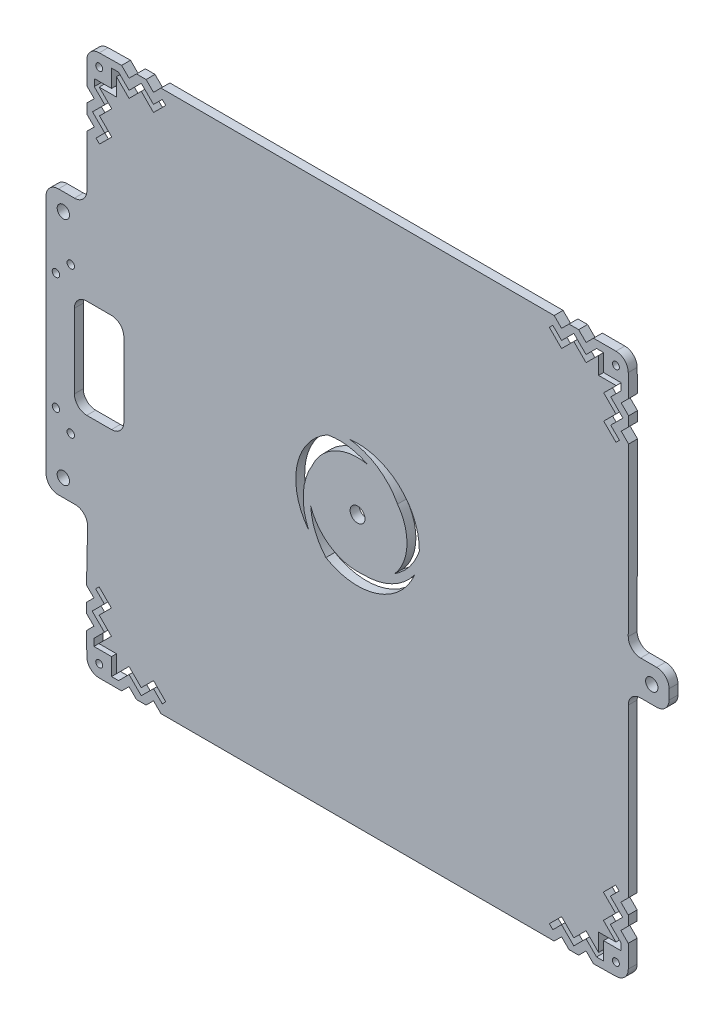
SolidWorks part; units mm, degrees
ref_plane "Front Plane" through (0, 0, 0) normal (0, 0, 1) x (1, 0, 0)
ref_plane "Top Plane" through (0, 0, 0) normal (0, 1, 0) x (1, 0, 0)
ref_plane "Right Plane" through (0, 0, 0) normal (1, 0, 0) x (0, 0, -1)
sketch "Model" plane through (0, 0, 0) normal (0, 0, 1) x (1, 0, 0)
  line L0 (-4, 125.6) -> (2.5, 125.6)
  line L1 (-4, 18.4) -> (2.8123, 18.4)
  line L2 (-9, 120.6) -> (-9, 23.4)
  line L3 (231.5, 82) -> (231.6, 82)
  line L4 (243, 74) -> (243, 70)
  line L5 (231.5, 62) -> (231.6, 62)
  line L10 (7.5, 151.5294) -> (7.5, 130.6)
  line L11 (7.5, 161.4289) -> (7.5, 157.5294)
  line L12 (7.5, 176.5) -> (7.5, 167.4289)
  line L13 (27.5711, 181.6421) -> (31.4706, 181.6421)
  line L14 (27.5711, -37.5) -> (31.4706, -37.5)
  line L15 (12.5, -37.5) -> (21.5711, -37.5)
  line L16 (7.3579, -17.4289) -> (7.3579, -13.5294)
  line L17 (226.5, -17.4289) -> (226.5, -13.5294)
  line L18 (226.5, -32.5) -> (226.5, -23.4289)
  line L19 (206.4289, -37.6421) -> (202.5294, -37.6421)
  line L20 (206.4289, 181.5) -> (202.5294, 181.5)
  line L21 (221.5, 181.5) -> (212.4289, 181.5)
  line L22 (226.6421, 161.4289) -> (226.6421, 157.5294)
  line L23 (14.7426, 154.5294) -> (9.7929, 159.4792)
  line L24 (14.7426, 164.4289) -> (9.7929, 159.4792)
  line L25 (17.5711, 164.4289) -> (12.6213, 159.4792)
  line L26 (17.5711, 154.5294) -> (12.6213, 159.4792)
  line L27 (17.5711, 164.4289) -> (12.5, 169.5)
  line L28 (14.7426, 164.4289) -> (10.5, 168.6716)
  line L29 (10.5, 168.6716) -> (10.5, 171.5)
  line L30 (10.5, 164.4289) -> (7.5, 161.4289)
  line L31 (10.5, 164.4289) -> (7.5, 167.4289)
  line L32 (10.5, 154.5294) -> (7.5, 151.5294)
  line L33 (10.5, 154.5294) -> (7.5, 157.5294)
  line L34 (34.4706, 174.3995) -> (29.5208, 179.3492)
  line L35 (24.5711, 174.3995) -> (29.5208, 179.3492)
  line L36 (24.5711, 171.5711) -> (29.5208, 176.5208)
  line L37 (34.4706, 171.5711) -> (29.5208, 176.5208)
  line L38 (24.5711, 171.5711) -> (19.5, 176.6421)
  line L39 (24.5711, 174.3995) -> (20.3284, 178.6421)
  line L40 (20.3284, 178.6421) -> (17.5, 178.6421)
  line L41 (24.5711, 178.6421) -> (27.5711, 181.6421)
  line L42 (24.5711, 178.6421) -> (21.5711, 181.6421)
  line L43 (34.4706, 178.6421) -> (37.4706, 181.6421)
  line L44 (34.4706, 178.6421) -> (31.4706, 181.6421)
  line L45 (17.5, 178.6421) -> (17.5, 171.5)
  line L46 (10.5, 171.5) -> (17.5, 171.5)
  line L47 (19.5, 176.6421) -> (19.5, 169.5)
  line L48 (12.5, 169.5) -> (19.5, 169.5)
  line L49 (21.5711, 181.6421) -> (12.5, 181.5)
  line L50 (34.4706, -30.2574) -> (29.5208, -35.2071)
  line L51 (24.5711, -30.2574) -> (29.5208, -35.2071)
  line L52 (24.5711, -27.4289) -> (29.5208, -32.3787)
  line L53 (34.4706, -27.4289) -> (29.5208, -32.3787)
  line L54 (24.5711, -27.4289) -> (19.5, -32.5)
  line L55 (24.5711, -30.2574) -> (20.3284, -34.5)
  line L56 (20.3284, -34.5) -> (17.5, -34.5)
  line L57 (24.5711, -34.5) -> (27.5711, -37.5)
  line L58 (24.5711, -34.5) -> (21.5711, -37.5)
  line L59 (34.4706, -34.5) -> (37.4706, -37.5)
  line L60 (34.4706, -34.5) -> (31.4706, -37.5)
  line L61 (14.6005, -10.5294) -> (9.6508, -15.4792)
  line L62 (14.6005, -20.4289) -> (9.6508, -15.4792)
  line L63 (17.4289, -20.4289) -> (12.4792, -15.4792)
  line L64 (17.4289, -10.5294) -> (12.4792, -15.4792)
  line L65 (17.4289, -20.4289) -> (12.3579, -25.5)
  line L66 (14.6005, -20.4289) -> (10.3579, -24.6716)
  line L67 (10.3579, -24.6716) -> (10.3579, -27.5)
  line L68 (10.3579, -20.4289) -> (7.3579, -17.4289)
  line L69 (10.3579, -20.4289) -> (7.3579, -23.4289)
  line L70 (10.3579, -10.5294) -> (7.3579, -7.5294)
  line L71 (10.3579, -10.5294) -> (7.3579, -13.5294)
  line L72 (10.3579, -27.5) -> (17.5, -27.5)
  line L73 (17.5, -34.5) -> (17.5, -27.5)
  line L74 (12.3579, -25.5) -> (19.5, -25.5)
  line L75 (19.5, -32.5) -> (19.5, -25.5)
  line L76 (7.3579, -23.4289) -> (7.5, -32.5)
  line L77 (219.2574, -10.5294) -> (224.2071, -15.4792)
  line L78 (219.2574, -20.4289) -> (224.2071, -15.4792)
  line L79 (216.4289, -20.4289) -> (221.3787, -15.4792)
  line L80 (216.4289, -10.5294) -> (221.3787, -15.4792)
  line L81 (216.4289, -20.4289) -> (221.5, -25.5)
  line L82 (219.2574, -20.4289) -> (223.5, -24.6716)
  line L83 (223.5, -24.6716) -> (223.5, -27.5)
  line L84 (223.5, -20.4289) -> (226.5, -17.4289)
  line L85 (223.5, -20.4289) -> (226.5, -23.4289)
  line L86 (223.5, -10.5294) -> (226.5, -7.5294)
  line L87 (223.5, -10.5294) -> (226.5, -13.5294)
  line L88 (199.5294, -30.3995) -> (204.4792, -35.3492)
  line L89 (209.4289, -30.3995) -> (204.4792, -35.3492)
  line L90 (209.4289, -27.5711) -> (204.4792, -32.5208)
  line L91 (199.5294, -27.5711) -> (204.4792, -32.5208)
  line L92 (209.4289, -27.5711) -> (214.5, -32.6421)
  line L93 (209.4289, -30.3995) -> (213.6716, -34.6421)
  line L94 (213.6716, -34.6421) -> (216.5, -34.6421)
  line L95 (209.4289, -34.6421) -> (206.4289, -37.6421)
  line L96 (209.4289, -34.6421) -> (212.4289, -37.6421)
  line L97 (199.5294, -34.6421) -> (196.5294, -37.6421)
  line L98 (199.5294, -34.6421) -> (202.5294, -37.6421)
  line L99 (216.5, -34.6421) -> (216.5, -27.5)
  line L100 (223.5, -27.5) -> (216.5, -27.5)
  line L101 (214.5, -32.6421) -> (214.5, -25.5)
  line L102 (221.5, -25.5) -> (214.5, -25.5)
  line L103 (212.4289, -37.6421) -> (221.5, -37.5)
  line L104 (199.5294, 174.2574) -> (204.4792, 179.2071)
  line L105 (209.4289, 174.2574) -> (204.4792, 179.2071)
  line L106 (209.4289, 171.4289) -> (204.4792, 176.3787)
  line L107 (199.5294, 171.4289) -> (204.4792, 176.3787)
  line L108 (209.4289, 171.4289) -> (214.5, 176.5)
  line L109 (209.4289, 174.2574) -> (213.6716, 178.5)
  line L110 (213.6716, 178.5) -> (216.5, 178.5)
  line L111 (209.4289, 178.5) -> (206.4289, 181.5)
  line L112 (209.4289, 178.5) -> (212.4289, 181.5)
  line L113 (199.5294, 178.5) -> (196.5294, 181.5)
  line L114 (199.5294, 178.5) -> (202.5294, 181.5)
  line L115 (219.3995, 154.5294) -> (224.3492, 159.4792)
  line L116 (219.3995, 164.4289) -> (224.3492, 159.4792)
  line L117 (216.5711, 164.4289) -> (221.5208, 159.4792)
  line L118 (216.5711, 154.5294) -> (221.5208, 159.4792)
  line L119 (216.5711, 164.4289) -> (221.6421, 169.5)
  line L120 (219.3995, 164.4289) -> (223.6421, 168.6716)
  line L121 (223.6421, 168.6716) -> (223.6421, 171.5)
  line L122 (223.6421, 164.4289) -> (226.6421, 161.4289)
  line L123 (223.6421, 164.4289) -> (226.6421, 167.4289)
  line L124 (223.6421, 154.5294) -> (226.6421, 151.5294)
  line L125 (223.6421, 154.5294) -> (226.6421, 157.5294)
  line L126 (223.6421, 171.5) -> (216.5, 171.5)
  line L127 (216.5, 178.5) -> (216.5, 171.5)
  line L128 (221.6421, 169.5) -> (214.5, 169.5)
  line L129 (214.5, 176.5) -> (214.5, 169.5)
  line L130 (226.6421, 167.4289) -> (226.5, 176.5)
  line L131 (37.4706, 181.6421) -> (196.5294, 181.5)
  line L132 (226.6421, 151.5294) -> (226.4934, 84.011)
  line L133 (226.5, 60) -> (226.5, -7.5294)
  line L134 (196.5294, -37.6421) -> (37.4706, -37.5)
  line L135 (7.3579, -7.5294) -> (7.8111, 13.2912)
  line L136 (14.6005, -10.5294) -> (11.065, -6.9939)
  line L137 (12.4792, -5.5797) -> (11.065, -6.9939)
  line L138 (17.4289, -10.5294) -> (12.4792, -5.5797)
  line L139 (34.4706, -30.2574) -> (38.0061, -33.7929)
  line L140 (39.4203, -32.3787) -> (38.0061, -33.7929)
  line L141 (34.4706, -27.4289) -> (39.4203, -32.3787)
  line L142 (216.4289, -10.5294) -> (221.3787, -5.5797)
  line L143 (221.3787, -5.5797) -> (222.7929, -6.9939)
  line L144 (219.2574, -10.5294) -> (222.7929, -6.9939)
  line L145 (199.5294, -27.5711) -> (194.5797, -32.5208)
  line L146 (194.5797, -32.5208) -> (195.9939, -33.935)
  line L147 (199.5294, -30.3995) -> (195.9939, -33.935)
  line L148 (199.5294, 174.2574) -> (195.9939, 177.7929)
  line L149 (194.5797, 176.3787) -> (195.9939, 177.7929)
  line L150 (199.5294, 171.4289) -> (194.5797, 176.3787)
  line L151 (219.3995, 154.5294) -> (222.935, 150.9939)
  line L152 (221.5208, 149.5797) -> (222.935, 150.9939)
  line L153 (216.5711, 154.5294) -> (221.5208, 149.5797)
  line L154 (34.4706, 174.3995) -> (38.0061, 177.935)
  line L155 (39.4203, 176.5208) -> (38.0061, 177.935)
  line L156 (34.4706, 171.5711) -> (39.4203, 176.5208)
  line L157 (14.7426, 154.5294) -> (11.2071, 150.9939)
  line L158 (12.6213, 149.5797) -> (11.2071, 150.9939)
  line L159 (17.5711, 154.5294) -> (12.6213, 149.5797)
  line L160 (238, 79) -> (231.4934, 79)
  line L161 (238, 65) -> (231.5, 65)
  line L163 (17.4584, 52) -> (7.4584, 52)
  line L164 (22.4584, 57) -> (22.4584, 87)
  line L165 (17.4584, 92) -> (7.4584, 92)
  line L166 (2.4584, 57) -> (2.4584, 87)
  arc A0 (-4, 18.4) -> (-9, 23.4) centre (-4, 23.4) cw
  arc A1 (7.8111, 13.2912) -> (2.8123, 18.4) centre (2.8123, 13.4) ccw
  arc A2 (-9, 120.6) -> (-4, 125.6) centre (-4, 120.6) cw
  arc A3 (231.4934, 79) -> (226.4934, 84.011) centre (231.4934, 84) cw
  arc A4 (12.5, 181.5) -> (7.5, 176.5) centre (12.5, 176.5) ccw
  arc A5 (226.5, 60) -> (231.5, 65) centre (231.5, 60) cw
  arc A6 (238, 79) -> (243, 74) centre (238, 74) cw
  arc A7 (243, 70) -> (238, 65) centre (238, 70) cw
  arc A8 (7.5, 130.6) -> (2.5, 125.6) centre (2.5, 130.6) cw
  arc A9 (7.5, -32.5) -> (12.5, -37.5) centre (12.5, -32.5) ccw
  arc A10 (221.5, -37.5) -> (226.5, -32.5) centre (221.5, -32.5) ccw
  arc A11 (226.5, 176.5) -> (221.5, 181.5) centre (221.5, 176.5) ccw
  circle A12 centre (-2, 118.6) radius 2.5
  circle A13 centre (-2, 25.4) radius 2.5
  circle A14 centre (236, 72) radius 2.5
  circle A15 centre (12.5, 176.5) radius 1.4
  circle A16 centre (117, 72) radius 3
  circle A17 centre (-5, 95.6) radius 1.5
  circle A18 centre (1, 101.6) radius 1.5
  arc A19 (98.7307, 80.1384) -> (97.2089, 56.7254) centre (120, 67) ccw
  arc A20 (98.0368, 65.6442) -> (104.1919, 50.5302) centre (123, 67) ccw
  arc A21 (119.0865, 52.1091) -> (140.1237, 62.4978) centre (119.8301, 77.0981) ccw
  arc A22 (131.9859, 58.7553) -> (141.9974, 71.6427) centre (118.3301, 79.6962) ccw
  arc A23 (133.1827, 83.7524) -> (113.6673, 96.7769) centre (111.1699, 71.9019) ccw
  arc A24 (120.9773, 91.6005) -> (104.8107, 93.8271) centre (109.6699, 69.3038) ccw
  arc A25 (141.9974, 71.6427) -> (113.6673, 96.7769) centre (117, 72) ccw
  arc A26 (104.1919, 50.5302) -> (140.1237, 62.4978) centre (117, 72) ccw
  arc A27 (104.8107, 93.8271) -> (97.2089, 56.7254) centre (117, 72) ccw
  arc A28 (120.9773, 91.6005) -> (98.7307, 80.1384) centre (117, 72) ccw
  arc A29 (131.9859, 58.7553) -> (133.1827, 83.7524) centre (117, 72) ccw
  arc A30 (98.0368, 65.6442) -> (119.0865, 52.1091) centre (117, 72) ccw
  circle A31 centre (12.5, -32.5) radius 1.4
  circle A32 centre (221.5, -32.5) radius 1.4
  circle A33 centre (221.5, 176.5) radius 1.4
  circle A34 centre (-5, 48.4) radius 1.5
  circle A35 centre (1, 42.4) radius 1.5
  arc A36 (2.4584, 57) -> (7.4584, 52) centre (7.4584, 57) ccw
  arc A37 (7.4584, 92) -> (2.4584, 87) centre (7.4584, 87) ccw
  arc A38 (22.4584, 87) -> (17.4584, 92) centre (17.4584, 87) ccw
  arc A39 (17.4584, 52) -> (22.4584, 57) centre (17.4584, 57) ccw
  point P76 (2.4584, 52)
  point P231 (2.4584, 92)
  point P234 (22.4584, 92)
  dimension "D2" = 119
  dimension "D3" = 119
  dimension "D4" = 30
  dimension "D5" = 30
  dimension "D6" = 7
  dimension "D7" = 7
  dimension "D8" = 7
  dimension "D9" = 7
  dimension "D10" = 7
  dimension "D11" = 7
  dimension "D12" = 5
  dimension "D13" = 5
  dimension "D14" = 5
  dimension "D15" = 5
  dimension "D16" = 5
  dimension "D17" = 5
  dimension "D18" = 5
  dimension "D19" = 5
  dimension "D20" = 20
  dimension "D25" = 5
  dimension "D26" = 5
  dimension "D27" = 5
  dimension "D28" = 5
  dimension "D1" = 119
  dimension "D21" = 40
  dimension "D22" = 20
  dimension "D23" = 24
  dimension "D24" = 24
extrude "Boss-Extrude1" add sketch "Model" along normal blind 3.6 contours A15 | L159 L26 L25 L27 L48 L47 L38 L36 L37 L156 L155 L154 L34 L35 L39 L40 L45 L46 L29 L28 L24 L23 L157 L158 | A17 | A18 | A12 | L163 A39 L164 A38 L165 A37 L166 A36 | A34 | A35 | A13 | L141 L53 L52 L54 L75 L74 L65 L63 L64 L138 L137 L136 L61 L62 L66 L67 L72 L73 L56 L55 L51 L50 L139 L140 | A31 | A16 | A29 A22 A25 A23 | A30 A20 A26 A21 | A28 A24 A27 A19 | A33 | L118 L153 L152 L151 L115 L116 L120 L121 L126 L127 L110 L109 L105 L104 L148 L149 L150 L107 L106 L108 L129 L128 L119 L117 | A32 | L147 L88 L89 L93 L94 L99 L100 L83 L82 L78 L77 L144 L143 L142 L80 L79 L81 L102 L101 L92 L90 L91 L145 L146 | A14 | L131 L113 L114 L20 L111 L112 L21 A11 L130 L123 L122 L22 L125 L124 L132 A3 L160 A6 L4 A7 L161 A5 L133 L86 L87 L17 L84 L85 L18 A10 L103 L96 L95 L19 L98 L97 L134 L59 L60 L14 L57 L58 L15 A9 L76 L69 L68 L16 L71 L70 L135 A1 L1 A0 L2 A2 L0 A8 L10 L32 L33 L11 L30 L31 L12 A4 L49 L42 L41 L13 L44 L43 region at (12.5648, 157.3013, 0) region at (31.6987, -32.4352, 0) region at (221.4352, -13.3013, 0) region at (202.3013, 176.4352, 0) region at (12.4584, 72, 0) region at (-2, 118.6, 0) region at (-2, 25.4, 0) region at (236, 72, 0) region at (12.5, 176.5, 0) region at (117, 72, 0) region at (-5, 95.6, 0) region at (1, 101.6, 0) region at (94.5791, 68.6523, 0) region at (105.9342, 54.7904, 0) region at (137.4525, 71.0208, 0) region at (12.5, -32.5, 0) region at (221.5, -32.5, 0) region at (221.5, 176.5, 0) region at (-5, 48.4, 0) region at (1, 42.4, 0)
